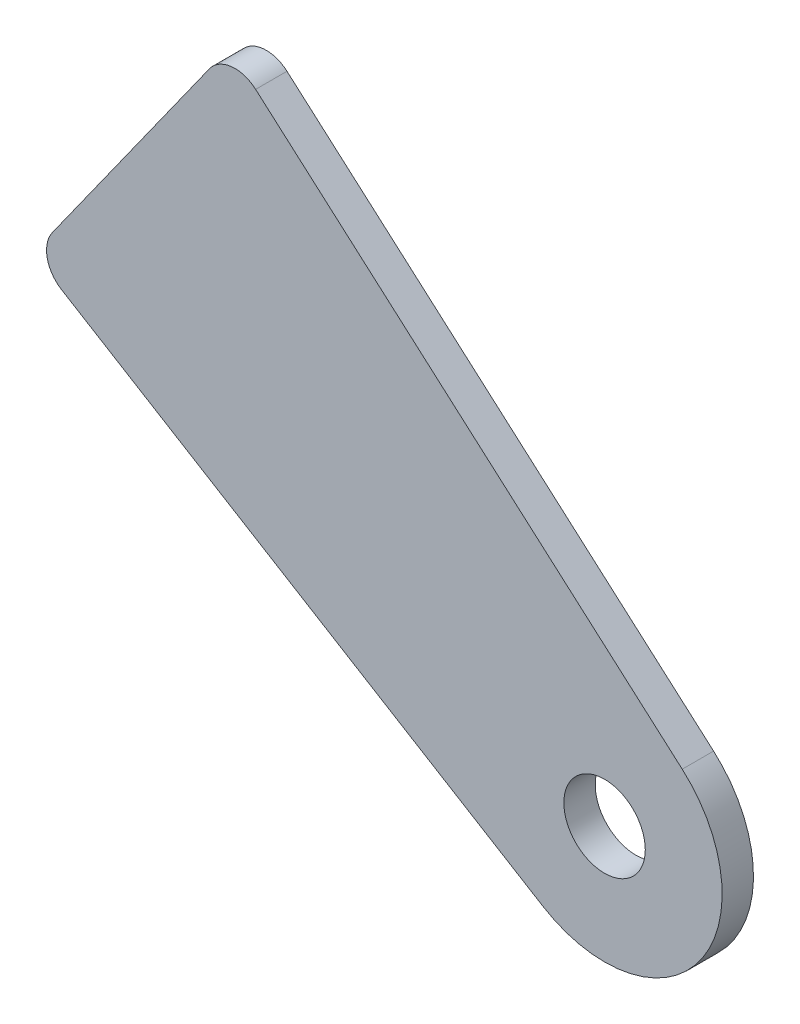
SolidWorks part; units mm, degrees
material "ASTM A36 Steel"
ref_plane "Front Plane" through (0, 0, 0) normal (0, 0, 1) x (1, 0, 0)
ref_plane "Top Plane" through (0, 0, 0) normal (0, 1, 0) x (1, 0, 0)
ref_plane "Right Plane" through (0, 0, 0) normal (1, 0, 0) x (0, 0, -1)
sketch "Sketch1" plane through (0, 0, 0) normal (0, 0, 1) x (1, 0, 0)
  line L0 (32.1903, -35.282) -> (-9.1733, -10.0799)
  line L1 (43.4392, -19.9977) -> (6.765, 12.2796)
  line L2 (-9.1733, -10.0799) -> (6.765, 12.2796)
  circle A2 centre (37.1463, -27.1479) radius 3.3
  circle A4 centre (37.1463, -27.1479) radius 9.525 construction
  arc A6 (43.4392, -19.9977) -> (32.1903, -35.282) centre (37.1463, -27.1479) cw
  dimension "D4" = 19.05
  dimension "D5" = 6.6
  dimension "D1" = 47.625
extrude "Boss-Extrude3" add sketch "Sketch1" along normal blind 2.54
fillet "Fillet1" radius 2.54 1 edges at (-9.1733, -10.0799, 1.27)
fillet "Fillet2" radius 2.54 1 edges at (6.765, 12.2796, 1.27)
